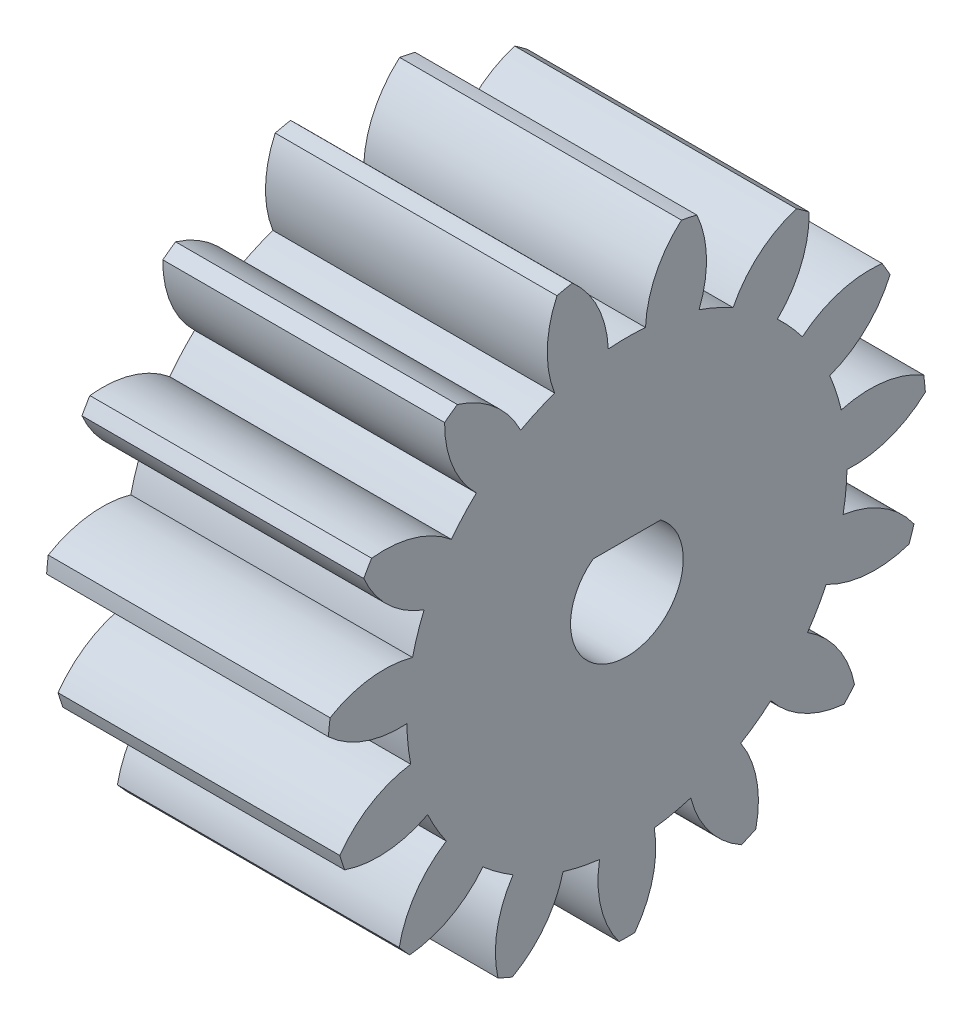
SolidWorks part; units mm, degrees
ref_plane "Plane1" through (0, 0, 0) normal (0, 0, 1) x (1, 0, 0)
ref_plane "Plane2" through (0, 0, 0) normal (0, 1, 0) x (1, 0, 0)
ref_plane "Plane3" through (0, 0, 0) normal (1, 0, 0) x (0, 0, -1)
sketch "HoldingSke" plane through (0, 0, 0) normal (0, 1, 0) x (1, 0, 0)
  line L0 (0, 0) -> (0.7727, -0.2071)
  line L1 (-15, 0) -> (100, 0) construction
  line L2 (0, 0) -> (-2.1039, 2.3779)
  line L3 (0, 0) -> (-11.863, 4.5341)
  line L4 (0, 0) -> (8.3417, 2.2352)
  line L5 (0, 0) -> (-46.8476, -17.4728)
  line L6 (0, 0) -> (-8.2896, -5.593)
  line L7 (-2.1039, 2.3779) -> (8.6586, 51.2059)
  line L8 (-76.2, 54.61) -> (-75.5, 54.61)
  line L9 (-71.009, 38.7566) -> (-53.1078, 45.2721)
  line L10 (-76.2, 71.12) -> (104.1128, 71.12)
  line L11 (0, 0) -> (-10, 0)
  line L12 (-76.2, 101.6) -> (-76.155, 101.6)
  line L13 (24.9733, 27.94) -> (52.9518, 28.4284)
  line L14 (24.9733, 27.94) -> (24.9743, 27.94)
  line L15 (24.9733, 27.94) -> (100.4006, 29.5858)
  line L16 (-63.627, -1.25) -> (-12.827, -1.25)
  circle A0 centre (0, 0) radius 2
  circle A1 centre (0, 0) radius 7.8115
  circle A2 centre (0, 0) radius 37.5
  circle A3 centre (0, 0) radius 2
  dimension "Num_teeth" = 15
  dimension "Pitch_radius" = 180.3128
  dimension "Width" = 10
  dimension "Thickness" = 10
sketch "BasProSke" plane through (0, 0, 0) normal (0, 1, 0) x (1, 0, 0)
  line L0 (-10, 0) -> (60, 0) construction
  line L1 (0, 0) -> (0, 10.625)
  line L2 (0, 0) -> (10, 0)
  line L3 (10, 0) -> (10, 10.625)
  line L4 (10, 10.625) -> (0, 10.625)
  dimension "Thickness" = 10
  dimension "Diameter" = 21.25
revolve "Base-Revolve" add sketch "BasProSke" angle 360 about L0
sketch "TooCutSke" plane through (0, 0, 0) normal (1, 0, 0) x (0, 0, -1)
  line L1 (0, 0) -> (0, 107) construction
  line L2 (0, 0) -> (-1.0586, 9.315) construction
  line L3 (0, 0) -> (-3.8803, 18.2553) construction
  line L4 (-1.0586, 9.315) -> (-1.9401, 9.1277) construction
  arc A0 (0.6608, 7.7835) -> (-0.6608, 7.7835) centre (0, 0) ccw
  arc A1 (1.9597, 10.4686) -> (-1.9597, 10.4686) centre (0, 0) ccw
  circle A2 centre (0, 0) radius 9.375 construction
  circle A3 centre (0, 0) radius 8.8096 construction
  arc A4 (-0.6608, 7.7835) -> (-1.9597, 10.4686) centre (-4.4076, 7.6277) ccw
  arc A5 (1.9597, 10.4686) -> (0.6608, 7.7835) centre (4.4076, 7.6277) ccw
extrude "ToothCut" cut sketch "TooCutSke" along normal through all
fillet "Breaks" [suppressed] radius 0.025 tangent propagation no
fillet "RootFillets" [suppressed] radius 0.3135
pattern_circular "TeethCuts" count 15 every 24 about axis through (-10, 0, 0) along (1, 0, 0) of "ToothCut", "RootFillets", "Breaks"
sketch "HubNeaOneSke" plane through (0, 0, 0) normal (-1, 0, 0) x (0, 0, 1)
  circle A0 centre (0, 0) radius 7.8115
  dimension "Diameter" = 15.623
extrude "HubNearOne" [suppressed] add sketch "HubNeaOneSke" along normal blind 40.0001
sketch "HubNeaBotSke" plane through (0, 0, 0) normal (-1, 0, 0) x (0, 0, 1)
  circle A0 centre (0, 0) radius 7.8115
  dimension "Diameter" = 15.623
extrude "HubNearBoth" [suppressed] add sketch "HubNeaBotSke" along normal blind 20
ref_plane "FarPln" through (10, 0, 0) normal (1, 0, 0) x (0, 0, -1)
sketch "HubFarSke" plane through (10, 0, 0) normal (1, 0, 0) x (0, 0, -1)
  circle A0 centre (0, 0) radius 7.8115
  dimension "Diameter" = 15.623
extrude "HubFar" [suppressed] add sketch "HubFarSke" along normal blind 20
sketch "BorSke" plane through (0, 0, 0) normal (1, 0, 0) x (0, 0, -1)
  circle A0 centre (0, 0) radius 2
  dimension "Diameter" = 4
extrude "Bore" cut sketch "BorSke" along normal mid plane 100.0001
sketch "KeySke" plane through (0, 0, 0) normal (1, 0, 0) x (0, 0, -1)
  line L0 (-0.8, 0) -> (-0.8, 2.7)
  line L1 (-0.8, 2.7) -> (0.8, 2.7)
  line L2 (0.8, 2.7) -> (0.8, 0)
  line L3 (0, 0) -> (0, 34) construction
  line L4 (-0.8, 0) -> (0.8, 0)
  dimension "Width" = 1.6
extrude "Keyway" [suppressed] cut sketch "KeySke" along normal mid plane 100.0001
pattern_circular "Keyway2" [suppressed] count 2 every 90 about axis through (-10, 0, 0) along (1, 0, 0) reverse direction yes
sketch "Sketch1" plane through (10, 0, 0) normal (1, 0, 0) x (0, 0, -1)
sketch "Sketch2" plane through (10, 0, 0) normal (1, 0, 0) x (0, 0, -1)
  line L0 (0, -2) -> (0, 1.6) construction
  line L1 (-1.2, 1.6) -> (1.2, 1.6)
  circle A0 centre (0, 0) radius 2 construction
  arc A1 (-1.2, 1.6) -> (1.2, 1.6) centre (0, 0) cw
extrude "Boss-Extrude1" add sketch "Sketch2" against normal blind 10 contours A1 L1 | A1 L1 region at (10, 1.7615, 0)
equation "' \"Module@HoldingSke\" = 6.35"
equation "' \"Num_teeth@HoldingSke\" = 12"
equation "' \"Ap@HoldingSke\" =  20"
equation "' \"Ap@HoldingSke\" = 20"
equation "' \"Width@HoldingSke\" = 0.5 * 25.4"
equation "' \"Hub_dia@HoldingSke\"= 1 * 25.4"
equation "' \"Hub_dia@HoldingSke\" = 1 * 25.4"
equation "' \"Overall_len@HoldingSke\" = 1.0 * 25.4"
equation "' \"Bore@HoldingSke\" = 0.75 * 25.4"
equation "' \"T_dim@HoldingSke\" = 0.1 * 25.4"
equation "' \"Width@KeySke\" = 0.25 * 25.4"
equation "' \"Show_teeth@HoldingSke\" = 13"
equation "' \"Backlash@HoldingSke\" = 0.009 * 25.4"
equation "' \"Addendum_fac@HoldingSke\" = 1.0"
equation "' \"Dedendum_fac@HoldingSke\" = 1.25"
equation "' \"Dedendum_add@HoldingSke\" = 0.00005 * 25.4"
equation "' \"Clearance_fac@HoldingSke\" = 0.25"
equation "\"Pitch@HoldingSke\" = 1 / \"Module@HoldingSke\""
equation "\"Overcut_dia@TooCutSke\" = (\"Num_teeth@HoldingSke\" + 2 * \"Addendum_fac@HoldingSke\") / \"Pitch@HoldingSke\" + 0.002 * 25.4"
equation "\"Pitch_dia@TooCutSke\" = \"Num_teeth@HoldingSke\" / \"Pitch@HoldingSke\""
equation "\"Base_dia@TooCutSke\" = \"Num_teeth@HoldingSke\" / \"Pitch@HoldingSke\" * cos((\"Ap@HoldingSke\"  * 3.14159265 / 180))"
equation "\"Root_dia@TooCutSke\" = (\"Num_teeth@HoldingSke\" + 2) / \"Pitch@HoldingSke\" - 2 * (\"Addendum_fac@HoldingSke\" + \"Dedendum_fac@HoldingSke\") / \"Pitch@HoldingSke\" - \"Dedendum_add@HoldingSke\" * 2"
equation "\"Half_ang@TooCutSke\" = 180 / \"Num_teeth@HoldingSke\""
equation "\"Half_CT@TooCutSke\" = \"Num_teeth@HoldingSke\" / \"Pitch@HoldingSke\" * sin((3.14159265 / 2 / \"Num_teeth@HoldingSke\")) / 2 - 7 * \"Backlash@HoldingSke\" / 4"
equation "\"Flank_rad@TooCutSke\" = \"Num_teeth@HoldingSke\" / \"Pitch@HoldingSke\" / 5"
equation "\"Radius@RootFillets\" = \"Clearance_fac@HoldingSke\" / \"Pitch@HoldingSke\" + \"Dedendum_add@HoldingSke\""
equation "\"Break_rad@Breaks\" = 0.02 / \"Pitch@HoldingSke\""
equation "\"Thickness@HoldingSke\" = \"Width@HoldingSke\""
equation "\"OAL@HoldingSke\" = \"Thickness@HoldingSke\""
equation "\"MHD@HoldingSke\" = (\"Num_teeth@HoldingSke\" + 2) / \"Pitch@HoldingSke\" - 2 * (\"Addendum_fac@HoldingSke\" + \"Dedendum_fac@HoldingSke\")  / \"Pitch@HoldingSke\" - \"Dedendum_add@HoldingSke\" * 2"
equation "\"MBD@HoldingSke\" = (\"Num_teeth@HoldingSke\" + 2) / \"Pitch@HoldingSke\" - 2 * (\"Addendum_fac@HoldingSke\" + \"Dedendum_fac@HoldingSke\")  / \"Pitch@HoldingSke\" - \"Dedendum_add@HoldingSke\" * 2 - 0.002 * 25.4"
equation "\"MHD@HoldingSke\" = ((sgn( \"MHD@HoldingSke\" - \"Hub_dia@HoldingSke\" )-1)*( \"MHD@HoldingSke\" - \"Hub_dia@HoldingSke\" ))/-2+ \"Hub_dia@HoldingSke\""
equation "\"MBD@HoldingSke\" = ((sgn( \"MBD@HoldingSke\" - \"Bore@HoldingSke\" )-1)*( \"MBD@HoldingSke\" - \"Bore@HoldingSke\" ))/-2+ \"Bore@HoldingSke\""
equation "\"OAL@HoldingSke\" = ((sgn( \"OAL@HoldingSke\" - \"Overall_len@HoldingSke\" )+1)*( \"OAL@HoldingSke\" - \"Overall_len@HoldingSke\" ))/2 + \"Overall_len@HoldingSke\" + 0.000002 * 25.4"
equation "\"Num_teeth@TeethCuts\" = int( \"Show_teeth@HoldingSke\" ) + 1"
equation "\"Num_teeth@TeethCuts\" = ((sgn( \"Num_teeth@TeethCuts\" - \"Num_teeth@HoldingSke\" )-1)*( \"Num_teeth@TeethCuts\" - \"Num_teeth@HoldingSke\" ))/-2+ \"Num_teeth@HoldingSke\""
equation "\"Num_teeth@TeethCuts\" = ((sgn( \"Num_teeth@TeethCuts\" - 2.0)+1)*( \"Num_teeth@TeethCuts\" - 2.0))/2 +2.0"
equation "\"Angle@TeethCuts\" = 360.0 / \"Num_teeth@HoldingSke\""
equation "\"Diameter@BasProSke\" = (\"Num_teeth@HoldingSke\" + 2 * \"Addendum_fac@HoldingSke\") / \"Pitch@HoldingSke\""
equation "\"Thickness@BasProSke\"  = \"Thickness@HoldingSke\""
equation "' \"Fillet_rad@BasProSke\" =  \"Thickness@HoldingSke\" * 0.05"
equation "' \"Fillet_rad@BasProSke\" = \"Thickness@HoldingSke\" * 0.05"
equation "\"MHD@HoldingSke\" = ((sgn( \"MHD@HoldingSke\" - \"Root_dia@TooCutSke\" )-1)*( \"MHD@HoldingSke\" - \"Root_dia@TooCutSke\" ))/-2+ \"Root_dia@TooCutSke\""
equation "\"Diameter@HubNeaOneSke\" = \"MHD@HoldingSke\""
equation "\"Length@HubNearOne\" = \"OAL@HoldingSke\" - \"Thickness@BasProSke\""
equation "\"Diameter@HubNeaBotSke\" = \"MHD@HoldingSke\""
equation "\"Length@HubNearBoth\" = ( \"OAL@HoldingSke\" - \"Thickness@BasProSke\" ) / 2.0"
equation "\"Thickness@FarPln\" = \"Thickness@BasProSke\""
equation "\"Diameter@HubFarSke\" = \"MHD@HoldingSke\""
equation "\"Length@HubFar\" = ( \"OAL@HoldingSke\" - \"Thickness@BasProSke\" ) / 2.0"
equation "\"Diameter@BorSke\" = \"MBD@HoldingSke\""
equation "\"D1@Bore\" = \"OAL@HoldingSke\" * 2.0"
equation "\"D1@Keyway\" = \"OAL@HoldingSke\" * 2.0"
equation "\"Offset@KeySke\" = \"T_dim@HoldingSke\" + \"MBD@HoldingSke\" / 2.0"
